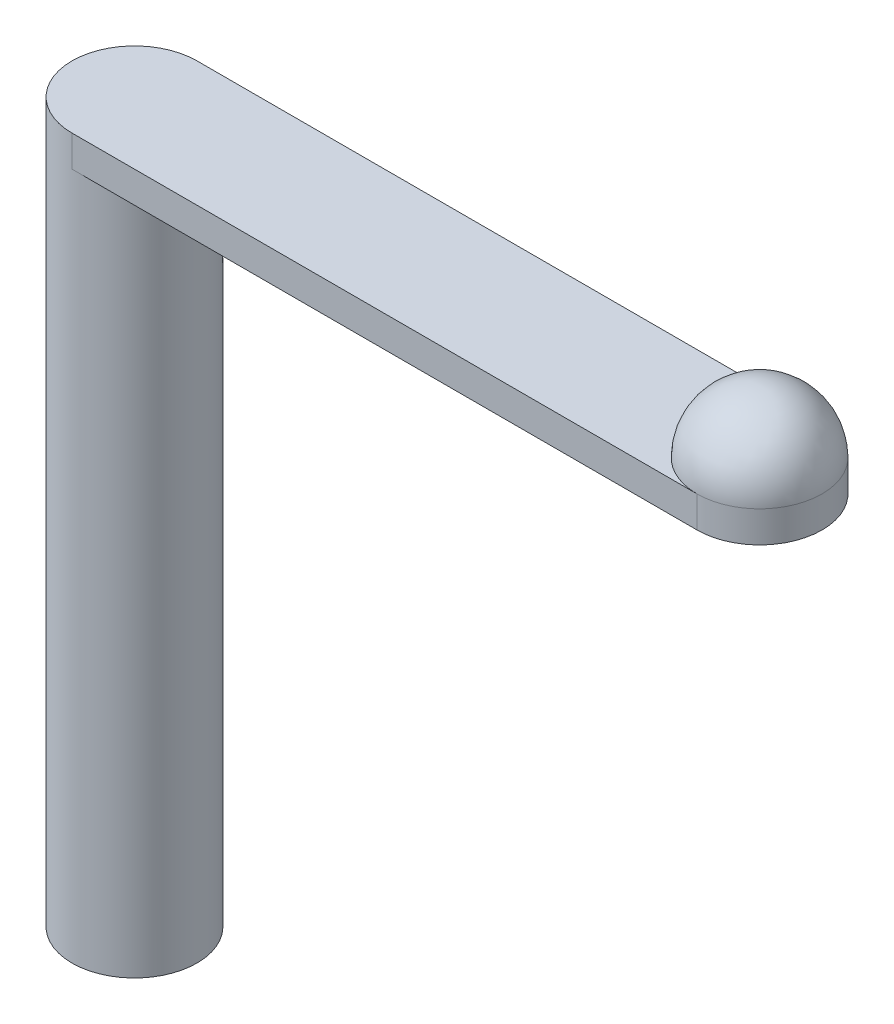
SolidWorks part; units mm, degrees
ref_plane "Front Plane" through (0, 0, 0) normal (0, 0, 1) x (1, 0, 0)
ref_plane "Top Plane" through (0, 0, 0) normal (0, 1, 0) x (1, 0, 0)
ref_plane "Right Plane" through (0, 0, 0) normal (1, 0, 0) x (0, 0, -1)
sketch "Sketch2" plane through (0, 0, 0) normal (0, 1, 0) x (1, 0, 0)
  circle A0 centre (0, 0) radius 10
  dimension "D1" = 20
extrude "Boss-Extrude1" add sketch "Sketch2" along normal blind 110
sketch "Sketch3" plane through (0, 110, 0) normal (0, 1, 0) x (1, 0, 0)
  line L0 (0, 10) -> (100, 10)
  line L1 (0, -10) -> (100, -10)
  arc A0 (0, 10) -> (0, -10) centre (0, 0) ccw
  circle A1 centre (0, 0) radius 10 construction
  arc A2 (100, 10) -> (100, -10) centre (100, 0) cw
extrude "Boss-Extrude2" add sketch "Sketch3" along normal blind 5
sketch "Sketch4" plane through (0, 115, 0) normal (0, 1, 0) x (1, 0, 0)
  circle A0 centre (100, 0) radius 10
extrude "Boss-Extrude3" add sketch "Sketch4" along normal blind 0.001
sketch "Sketch5" plane through (0, 115.001, 0) normal (0, 1, 0) x (1, 0, 0)
  circle A0 centre (100, 0) radius 10
extrude "Boss-Extrude4" add sketch "Sketch5" along normal blind 10
fillet "Fillet1" radius 10 1 edges at (100, 125.001, 10)
